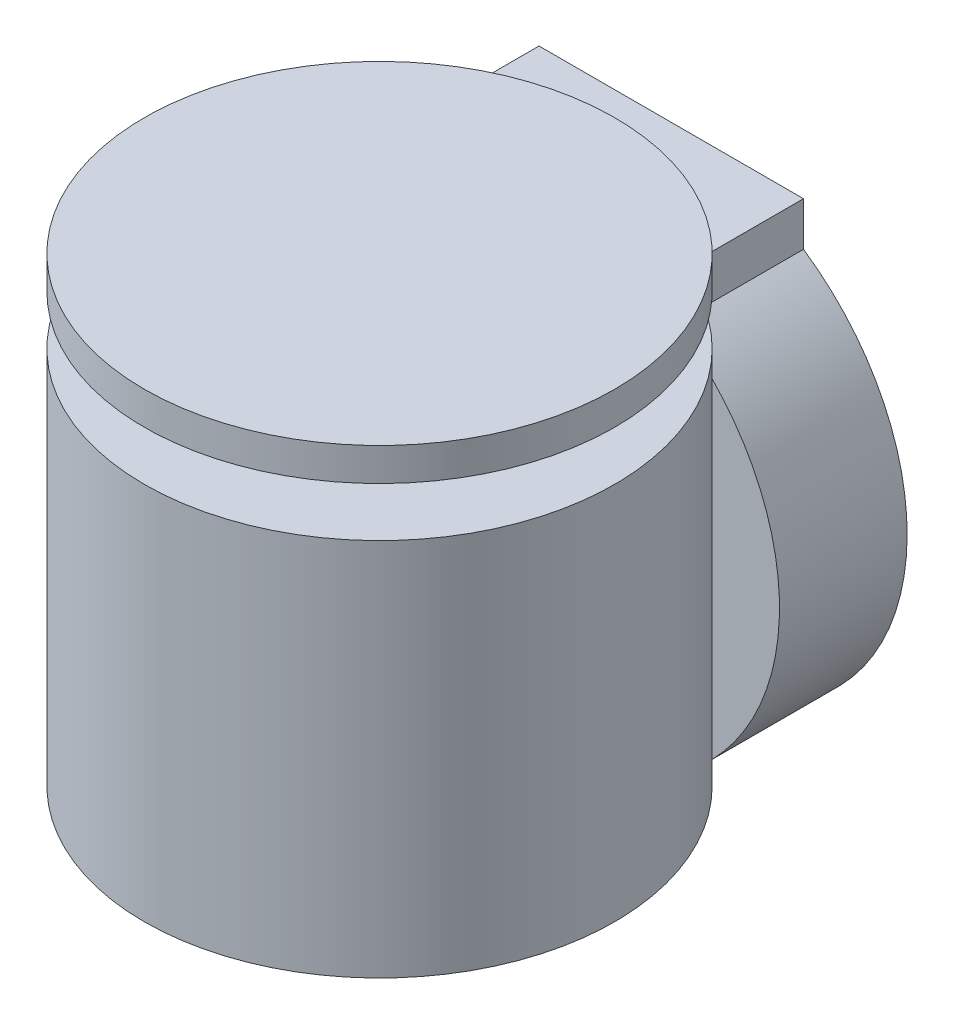
SolidWorks part; units mm, degrees
ref_plane "Front Plane" through (0, 0, 0) normal (0, 0, 1) x (1, 0, 0)
ref_plane "Top Plane" through (0, 0, 0) normal (0, 1, 0) x (1, 0, 0)
ref_plane "Right Plane" through (0, 0, 0) normal (1, 0, 0) x (0, 0, -1)
sketch "Sketch1" plane through (0, 0, 0) normal (0, 1, 0) x (1, 0, 0)
  circle A0 centre (0, 0) radius 0.0286
extrude "Boss-Extrude1" add sketch "Sketch1" along normal blind 0.023 and the other way blind 0.023
extrude "Boss-Extrude2" add sketch "Sketch1<2>" along normal blind 0.004 from offset 0.029 separate body
sketch "Sketch1<2>" plane through (0, 0, 0) normal (0, 1, 0) x (1, 0, 0) same geometry as "Sketch1"
sketch "Sketch2" plane through (0, 0, 0) normal (0, 0, 1) x (1, 0, 0)
  line L0 (-0.0286, 0.029) -> (0.0286, 0.029) construction
  line L2 (-0.0161, 0.0236) -> (-0.0161, 0.029)
  line L5 (0.016, 0.029) -> (-0.0161, 0.029)
  line L6 (0.016, 0.029) -> (0.016, 0.0237)
  arc A0 (-0.0161, 0.0236) -> (0.016, 0.0237) centre (0, 0) ccw
extrude "Boss-Extrude3" add sketch "Sketch2" against normal blind 0.0155 from offset 0.02 offset against normal yes
